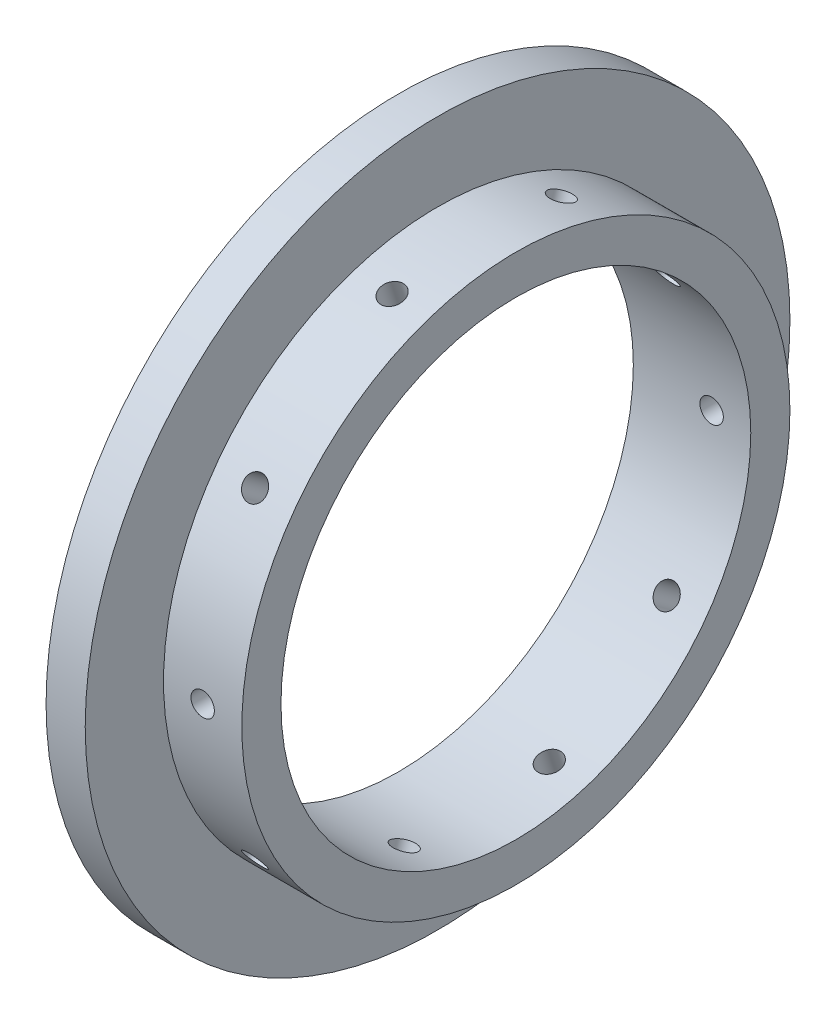
SolidWorks part; units mm, degrees
material "7075-T6 (SN)"
ref_plane "Front Plane" through (0, 0, 0) normal (0, 0, 1) x (1, 0, 0)
ref_plane "Top Plane" through (0, 0, 0) normal (0, 1, 0) x (1, 0, 0)
ref_plane "Right Plane" through (0, 0, 0) normal (1, 0, 0) x (0, 0, -1)
sketch "Sketch1" plane through (0, 0, 0) normal (1, 0, 0) x (0, 0, -1)
  circle A0 centre (0, 0) radius 38.1
  circle A1 centre (0, 0) radius 57.15
  dimension "D1" = 76.2
  dimension "D2" = 114.3
extrude "Boss-Extrude1" add sketch "Sketch1" along normal blind 6.35
sketch "Sketch2" plane through (6.35, 0, 0) normal (1, 0, 0) x (0, 0, -1)
  circle A0 centre (0, 0) radius 44.45
  circle A1 centre (0, 0) radius 38.1
  dimension "D1" = 88.9
  dimension "D2" = 76.2
extrude "Boss-Extrude2" add sketch "Sketch2" along normal blind 12.7
sketch "Sketch3" plane through (0, 0, 0) normal (0, 1, 0) x (1, 0, 0)
  line L0 (0, 0) -> (88.5884, 0) construction
  line L1 (-13.97, 0) -> (13.97, 0) construction
  line L2 (0, 0) -> (0, 82.8947) construction
ref_plane "Plane1" through (0, 0, -44.45) normal (0, 0, -1) x (-1, 0, 0)
sketch "Sketch4" plane through (0, 0, -44.45) normal (0, 0, -1) x (-1, 0, 0)
  line L0 (0, 0) -> (-88.5884, 0) construction
  line L2 (-6.35, 44.45) -> (-6.35, -44.45) construction
  circle A0 centre (-12.7, 0) radius 1.8986
  dimension "D2" = 3.7973
  dimension "D1" = 6.35
extrude "Cut-Extrude1" cut sketch "Sketch4" against normal blind 7.62
pattern_circular "CirPattern1" count 10 every 36 about axis through (0, 0, 0) along (1, 0, 0) of "Cut-Extrude1"
